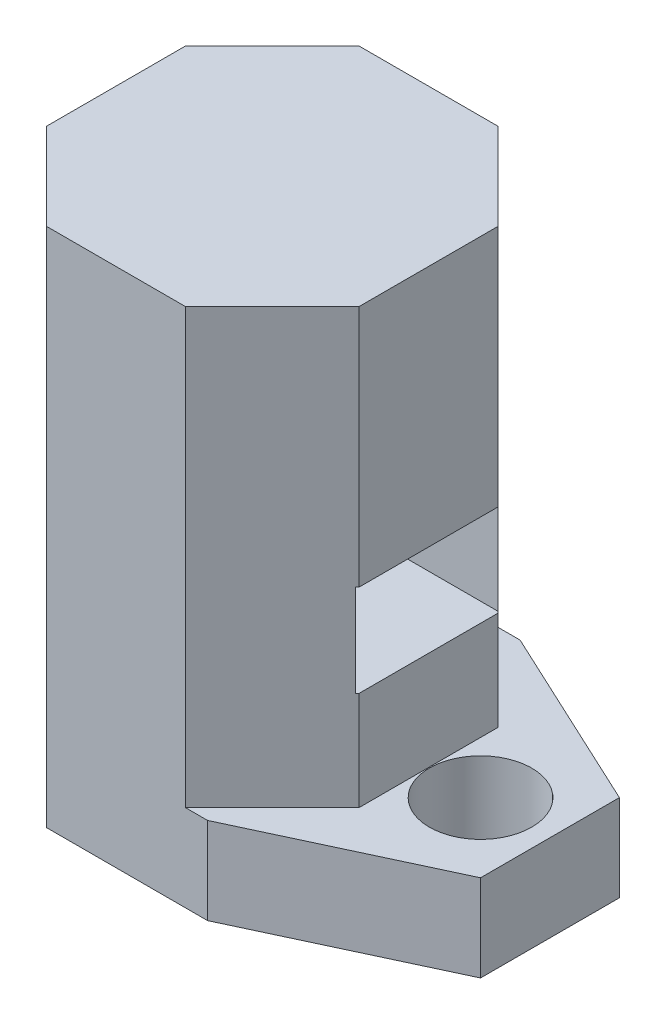
SolidWorks part; units mm, degrees
ref_plane "Front Plane" through (0, 0, 0) normal (0, 0, 1) x (1, 0, 0)
ref_plane "Top Plane" through (0, 0, 0) normal (0, 1, 0) x (1, 0, 0)
ref_plane "Right Plane" through (0, 0, 0) normal (1, 0, 0) x (0, 0, -1)
sketch "Sketch1" plane through (0, 0, 0) normal (0, 0, 1) x (1, 0, 0)
  line L1 (4, 0) -> (4, -30)
  line L2 (4, -30) -> (-14, -30)
  line L3 (-14, -30) -> (-14, 0)
  line L5 (-14, 0) -> (4, 0)
  line L10 (0, -8.25) -> (0, 8.25) construction
  line L11 (8.25, 0) -> (-8.25, 0) construction
  dimension "D4" = 18
  dimension "D5" = 30
  dimension "D7" = 4
extrude "Boss-Extrude1" add sketch "Sketch1" along normal mid plane 18
sketch "Sketch2" plane through (0, -30, 0) normal (0, -1, 0) x (1, 0, 0)
  line L0 (9.9, 0) -> (-9.9, 0) construction
  line L1 (-14, 9) -> (-14, -9) construction
  circle A0 centre (-5, 0) radius 5.25
  dimension "D1" = 10.5
  dimension "D2" = 9
extrude "Cut-Extrude1" cut sketch "Sketch2" against normal blind 6
sketch "Sketch4" plane through (0, -30, 0) normal (0, -1, 0) x (1, 0, 0)
  circle A0 centre (-5, 0) radius 2.75
  dimension "D1" = 5.5
extrude "Cut-Extrude3" cut sketch "Sketch4" against normal blind 28
sketch "Sketch5" plane through (4, 0, 0) normal (1, 0, 0) x (0, 0, -1)
  line L0 (0, 13.75) -> (0, -13.75) construction
  line L1 (-4.1, -14) -> (4.1, -14)
  line L2 (-4.1, -14) -> (-4.1, -19.3)
  line L3 (-4.1, -19.3) -> (4.1, -19.3)
  line L4 (4.1, -14) -> (4.1, -19.3)
  line L5 (9.9, 0) -> (-9.9, 0) construction
  dimension "D1" = 8.2
  dimension "D2" = 4.1
  dimension "D3" = 5.3
  dimension "D4" = 14
extrude "Cut-Extrude4" cut sketch "Sketch5" against normal up to next
chamfer "Chamfer3" distance 5 angle 45 4 edges at (-14, -15, 9) (-14, -15, -9) (4, -15, -9) (4, -15, 9)
sketch "Sketch6" plane through (0, -30, 0) normal (0, -1, 0) x (1, 0, 0)
  line L0 (-1, -9) -> (11, -9)
  line L1 (11, -9) -> (11, 9)
  line L3 (4, 4) -> (4, -4)
  line L4 (4, -4) -> (-1, -9)
  line L5 (-1, 9) -> (11, 9)
  line L6 (-1, 9) -> (4, 4)
  circle A0 centre (7, 0) radius 2.95
  dimension "D2" = 5.9
  dimension "D1" = 12
  dimension "D3" = 4
  dimension "D4" = 9
extrude "Boss-Extrude2" add sketch "Sketch6" against normal blind 5
chamfer "Chamfer4" distance 5 angle 65 2 edges at (11, -27.5, -9) (11, -27.5, 9) first distance on face at (11, -27.5, 0)
